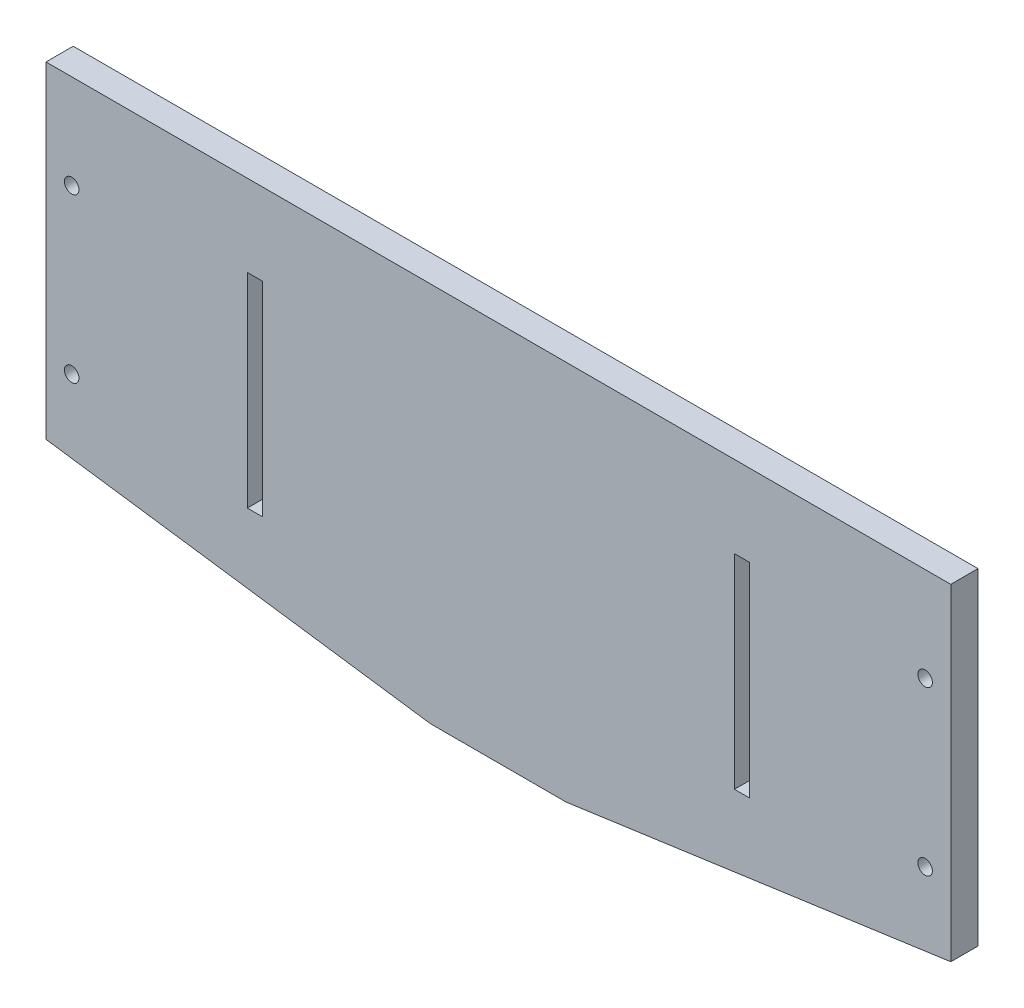
SolidWorks part; units mm, degrees
material "Acrylic (Medium-high impact)"
ref_plane "Front Plane" through (0, 0, 0) normal (0, 0, 1) x (1, 0, 0)
ref_plane "Top Plane" through (0, 0, 0) normal (0, 1, 0) x (1, 0, 0)
ref_plane "Right Plane" through (0, 0, 0) normal (1, 0, 0) x (0, 0, -1)
sketch "Sketch1" plane through (0, 0, 0) normal (0, 0, 1) x (1, 0, 0)
  line L1 (211.1756, 127) -> (0, 127)
  line L2 (211.1756, 127) -> (211.1756, 0)
  line L3 (211.1756, 0) -> (0, 0)
  line L4 (0, 127) -> (0, 0)
  line L5 (211.1756, 127) -> (0, 0) construction
  line L6 (211.1756, 0) -> (0, 127) construction
  point P0 (105.5878, 63.5)
  dimension "D1" = 127
  dimension "D2" = 211.1756
extrude "Boss-Extrude1" add sketch "Sketch1" along normal blind 6.35
hole_wizard "M3 Clearance Hole1" positions "Sketch2" profile "Sketch3" hole size "M3" standard "ANSI Metric" end condition through all
sketch "Sketch2" plane through (0, 0, 6.35) normal (0, 0, 1) x (1, 0, 0)
  line L0 (0, 127) -> (0, 0) construction
  line L1 (211.1756, 127) -> (0, 127) construction
  line L2 (211.1756, 0) -> (211.1756, 127) construction
  point P0 (5.9944, 105.0036)
  point P2 (5.9944, 66.9036)
  point P4 (205.1812, 66.9036)
  point P6 (205.1812, 105.0036)
  dimension "D1" = 5.9944
  dimension "D2" = 21.9964
  dimension "D3" = 5.9944
  dimension "D4" = 38.1
sketch "Sketch3" plane through (5.9944, 105.0036, 6.35) normal (1, 0, 0) x (0, -1, 0)
  line L0 (0, 0) -> (0, 6.35)
  line L1 (0, 6.35) -> (1.7, 6.35)
  line L2 (1.7, 6.35) -> (1.7, 0)
  line L5 (1.7, 0) -> (0, 0)
  line L11 (0, -6.35) -> (0, 107.95) construction
  dimension "Thru Hole Dia." = 3.4
  dimension "Thru Hole Depth" = 6.35
sketch "Sketch4" plane through (0, 0, 6.35) normal (0, 0, 1) x (1, 0, 0)
  line L0 (0, 127) -> (0, 0) construction
  line L1 (46.99, 107.95) -> (50.4952, 107.95)
  line L2 (46.99, 107.95) -> (46.99, 60.325)
  line L3 (46.99, 60.325) -> (50.4952, 60.325)
  line L4 (50.4952, 107.95) -> (50.4952, 60.325)
  line L5 (160.6804, 107.95) -> (164.1856, 107.95)
  line L6 (160.6804, 107.95) -> (160.6804, 60.325)
  line L7 (160.6804, 60.325) -> (164.1856, 60.325)
  line L8 (164.1856, 107.95) -> (164.1856, 60.325)
  line L9 (211.1756, 0) -> (211.1756, 127) construction
  line L10 (211.1756, 127) -> (0, 127) construction
  dimension "D1" = 3.5052
  dimension "D2" = 47.625
  dimension "D3" = 46.99
  dimension "D4" = 46.99
  dimension "D5" = 19.05
extrude "Cut-Extrude1" cut sketch "Sketch4" against normal through all
sketch "Sketch5" plane through (0, 0, 6.35) normal (0, 0, 1) x (1, 0, 0)
  line L0 (0, 50.7083) -> (89.7128, 38.1)
  line L1 (0, 127) -> (0, 0) construction
  line L2 (89.7128, 38.1) -> (121.4628, 38.1)
  line L3 (121.4628, 38.1) -> (211.1756, 50.7083)
  line L4 (211.1756, 0) -> (211.1756, 127) construction
  line L5 (211.1756, 50.7083) -> (211.1756, 0)
  line L6 (211.1756, 0) -> (0, 0)
  line L7 (0, 0) -> (0, 50.7083)
  dimension "D1" = 8
  dimension "D2" = 8
  dimension "D3" = 31.75
  dimension "D5" = 38.1
extrude "Cut-Extrude2" cut sketch "Sketch5" against normal through all
